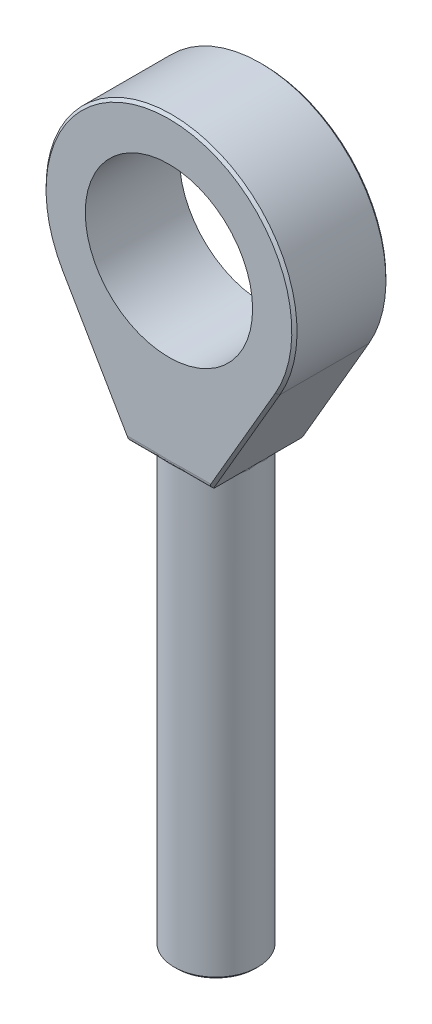
SolidWorks part; units mm, degrees
ref_plane "Front Plane" through (0, 0, 0) normal (0, 0, 1) x (1, 0, 0)
ref_plane "Top Plane" through (0, 0, 0) normal (0, 1, 0) x (1, 0, 0)
ref_plane "Right Plane" through (0, 0, 0) normal (1, 0, 0) x (0, 0, -1)
sketch "Sketch1" plane through (0, 0, 0) normal (0, 0, 1) x (1, 0, 0)
  line L0 (0, 0) -> (0, -42) construction
  line L3 (4, -17) -> (10.3753, -6.0293)
  line L5 (-4, -17) -> (-10.3753, -6.0293)
  line L6 (-4, -17) -> (4, -17)
  arc A0 (10.3753, -6.0293) -> (-10.3753, -6.0293) centre (0, 0) ccw
  circle A1 centre (0, 0) radius 8
  dimension "D1" = 8
  dimension "D2" = 24
  dimension "D3" = 16
extrude "Boss-Extrude1" add sketch "Sketch1" along normal mid plane 9
ref_plane "Plane1" through (0, -17, 0) normal (0, -1, 0) x (-1, 0, 0)
sketch "Sketch2" plane through (0, -17, 0) normal (0, -1, 0) x (1, 0, 0)
  circle A0 centre (0, 0) radius 4
extrude "Boss-Extrude2" add sketch "Sketch2" along normal blind 42
chamfer "Chamfer1" distance 0.25 angle 45 6 edges at (7.1877, -11.5147, -4.5) (-7.1877, -11.5147, -4.5) (0, 12, -4.5) (7.1877, -11.5147, 4.5) (-7.1877, -11.5147, 4.5) (0, 12, 4.5)
chamfer "Chamfer3" distance 0.25 angle 45 1 edges at (4, -59, 0)
fillet "Fillet5" radius 0.25 2 edges at (0, -17, -4) (0, -17, 4)
fillet "Fillet6" radius 0.5 2 edges at (0, -17, -4.5) (0, -17, 4.5)
sketch "Sketch3" plane through (0, 0, 0) normal (0, 1, 0) x (1, 0, 0)
  line L0 (0, 8.3155) -> (0, -9.5229) construction
